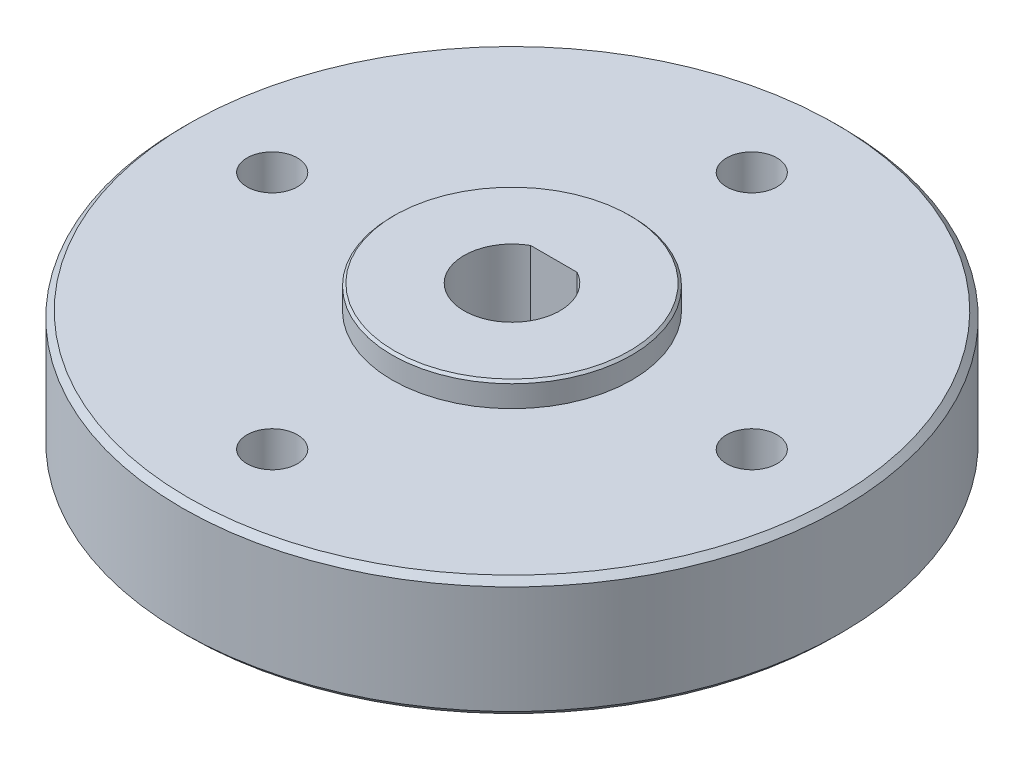
SolidWorks part; units mm, degrees
ref_plane "Plan de face" through (0, 0, 0) normal (0, 0, 1) x (1, 0, 0)
ref_plane "Plan de dessus" through (0, 0, 0) normal (0, 1, 0) x (1, 0, 0)
ref_plane "Plan de droite" through (0, 0, 0) normal (1, 0, 0) x (0, 0, -1)
sketch "Esquisse1" plane through (0, 0, 0) normal (0, 1, 0) x (1, 0, 0)
  line L0 (-1.9365, 3.5) -> (1.9365, 3.5)
  line L1 (-14.7962, -4) -> (15.1847, -4) construction
  arc A0 (-1.9365, 3.5) -> (1.9365, 3.5) centre (0, 0) ccw
  circle A1 centre (0, 0) radius 10
  dimension "D1" = 8
  dimension "D2" = 20
  dimension "D3" = 7.5
extrude "Boss.-Extru.1" add sketch "Esquisse1" along normal blind 10
ref_plane "Plan1" through (0, 0, -10) normal (0, 0, -1) x (-1, 0, 0)
hole_wizard "Dégagement M41" positions "Esquisse2" profile "Esquisse3" hole size "M4" standard "ISO"
sketch "Esquisse2" plane through (0, 0, -10) normal (0, 0, -1) x (-1, 0, 0)
  line L0 (0, 24.6467) -> (0, -10.1954) construction
  line L2 (12.6538, 5) -> (-9.1277, 5) construction
  line L4 (-10, 0) -> (10, 0) construction
  line L5 (10, 10) -> (-10, 10) construction
  point P0 (0, 5)
sketch "Esquisse3" plane through (0, 5, -10) normal (1, 0, 0) x (0, 1, 0)
  line L0 (0, 0) -> (0, 9.2919)
  line L1 (0, 9.2919) -> (2.15, 8)
  line L2 (2.15, 8) -> (2.15, 0)
  line L5 (2.15, 0) -> (0, 0)
  line L10 (0, 9.2919) -> (-2.15, 8) construction
  line L11 (0, -6.35) -> (0, 107.95) construction
  dimension "Diamètre du perçage" = 4.3
  dimension "Profondeur du perçage" = 8
  dimension "Angle de pointe" = 118
sketch "Esquisse4" plane through (0, 10, 0) normal (0, 1, 0) x (1, 0, 0)
  line L0 (-1.9365, 3.5) -> (1.9365, 3.5)
  circle A0 centre (0, 0) radius 27.5
  arc A1 (-1.9365, 3.5) -> (1.9365, 3.5) centre (0, 0) ccw
  arc A2 (-1.9365, 3.5) -> (1.9365, 3.5) centre (0, 0) ccw construction
  dimension "D1" = 55
extrude "Boss.-Extru.2" add sketch "Esquisse4" along normal blind 10
sketch "Esquisse5" plane through (0, 20, 0) normal (0, 1, 0) x (1, 0, 0)
  line L0 (1.9365, 3.5) -> (-1.9365, 3.5) construction
  line L1 (-1.9365, 3.5) -> (1.9365, 3.5)
  circle A0 centre (0, 0) radius 10
  arc A1 (-1.9365, 3.5) -> (1.9365, 3.5) centre (0, 0) ccw
  dimension "D1" = 20
extrude "Boss.-Extru.3" add sketch "Esquisse5" along normal blind 2
hole_wizard "Trou pour taraudage pour trou taraudé M51" positions "Esquisse8" profile "Esquisse7" hole size "M5" standard "ISO" end condition through all
sketch "Esquisse8" plane through (0, 20, 0) normal (0, 1, 0) x (1, 0, 0)
  line L0 (0, -41.259) -> (0, 33.9373) construction
  circle A0 centre (0, 0) radius 20 construction
  point P0 (0, -20)
  dimension "D1" = 40
sketch "Esquisse7" plane through (0, 20, 20) normal (1, 0, 0) x (0, 0, 1)
  line L0 (0, 0) -> (0, 20)
  line L1 (0, 20) -> (2.1, 20)
  line L2 (2.1, 20) -> (2.1, 0)
  line L5 (2.1, 0) -> (0, 0)
  line L11 (0, -6.35) -> (0, 107.95) construction
  dimension "Diamètre du perçage jusqu'au prochain" = 4.2
  dimension "Profondeur du perçage jusqu'au prochain" = 20
ref_axis "Axe1" through (0, 22, 0) along (0, -1, 0)
pattern_circular "Répétition circulaire1" count 4 over 360 about axis through (0, 22, 0) along (0, -1, 0) of "Trou pour taraudage pour trou taraudé M51"
chamfer "Chanfrein1" distance 0.5 angle 45 3 edges at (0, 0, 10) (0, 10, 27.5) (0, 20, 27.5)
chamfer "Chanfrein2" distance 0.2 angle 45 1 edges at (0, 22, 10)
